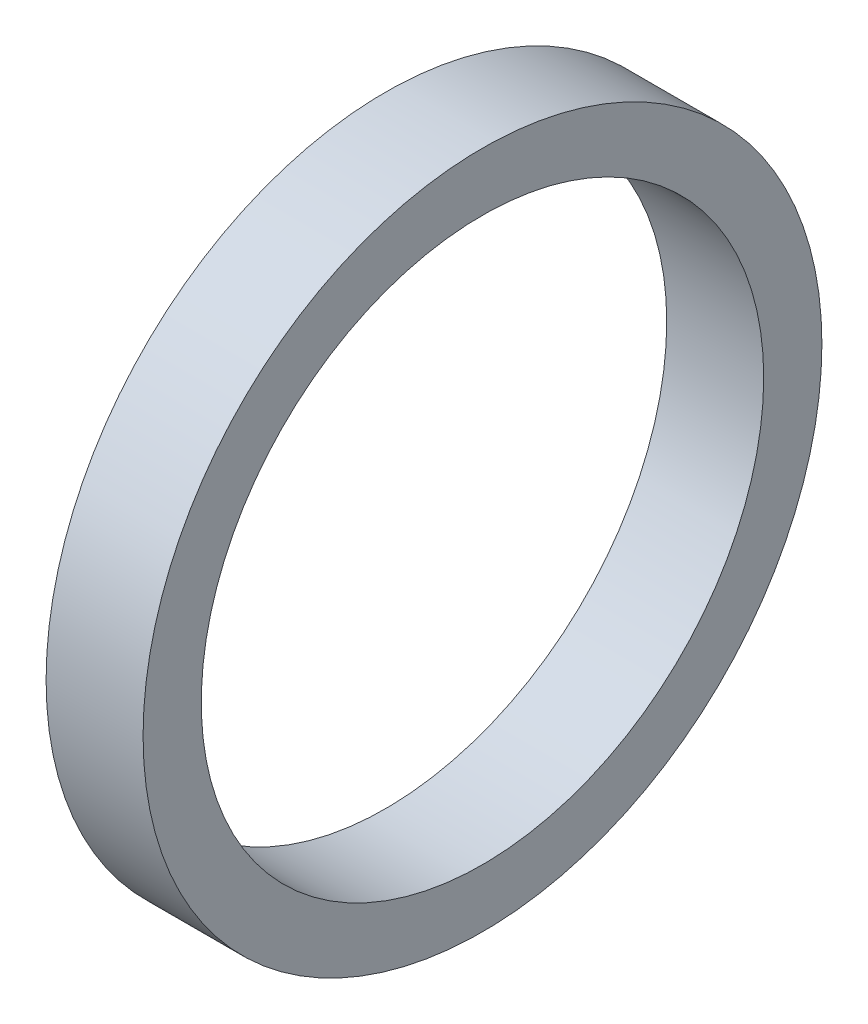
SolidWorks part; units mm, degrees
ref_plane "Front Plane" through (0, 0, 0) normal (0, 0, 1) x (1, 0, 0)
ref_plane "Top Plane" through (0, 0, 0) normal (0, 1, 0) x (1, 0, 0)
ref_plane "Right Plane" through (0, 0, 0) normal (1, 0, 0) x (0, 0, -1)
sketch "Sketch1" plane through (0, 0, 0) normal (1, 0, 0) x (0, 0, -1)
  circle A0 centre (0, 0) radius 29
  circle A1 centre (0, 0) radius 35
extrude "Boss-Extrude1" add sketch "Sketch1" along normal blind 10
